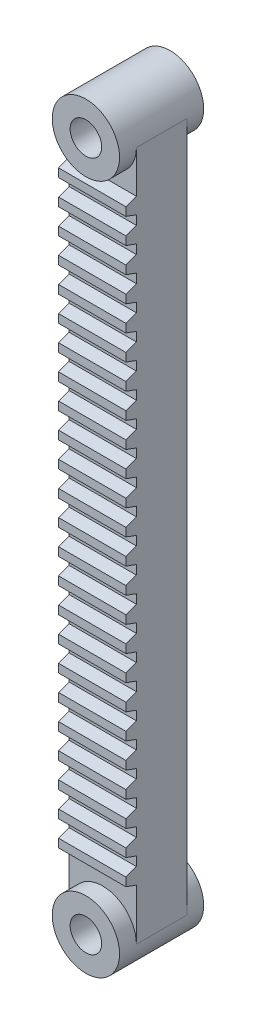
SolidWorks part; units mm, degrees
ref_plane "Front Plane" through (0, 0, 0) normal (1, 0, 0) x (0, 1, 0)
ref_plane "Top Plane" through (0, 0, 0) normal (0, 0, 1) x (0, 1, 0)
ref_plane "Right Plane" through (0, 0, 0) normal (0, 1, 0) x (-1, 0, 0)
sketch "Sketch3" plane through (0, 0, 0) normal (0, 0, 1) x (0, 1, 0)
  line L1 (-82, -8) -> (82, -8)
  line L3 (-82, 8) -> (82, 8)
  line L5 (-82, -8) -> (82, 8) construction
  line L6 (-82, 8) -> (82, -8) construction
  circle A0 centre (-82, 0) radius 8
  circle A1 centre (82, 0) radius 8
  circle A2 centre (-82, 0) radius 3.75
  circle A3 centre (82, 0) radius 3.75
  point P0 (0, 0)
  dimension "D1" = 16
  dimension "D2" = 16
  dimension "D5" = 7.5
  dimension "D6" = 7.5
  dimension "D3" = 164
  dimension "D4" = 16
extrude "Boss-Extrude1" add sketch "Sketch3" along normal blind 12 contours A1 L3 A0 L1 region at (0, 0, 0)
extrude "Boss-Extrude2" add sketch "Sketch3<3>" along normal blind 20 from offset 4 contours A0 A2 | A1 A3 region at (0, -89.7737, 0) region at (0, 74.2263, 0) offset against normal yes
sketch "Sketch3<3>" plane through (0, 0, 0) normal (0, 0, 1) x (0, 1, 0) same geometry as "Sketch3"
sketch "Sketch4" plane through (0, 0, 0) normal (1, 0, 0) x (0, 1, 0)
  line L0 (72, 12) -> (71.0901, 14.5)
  line L1 (-82, 12) -> (82, 12) construction
  line L2 (71.0901, 14.5) -> (69.0901, 14.5)
  line L3 (69.0901, 14.5) -> (68.1801, 12)
  line L4 (68.1801, 12) -> (72, 12)
  dimension "D1" = 2.5
  dimension "D2" = 2
  dimension "D3" = 40
  dimension "D4" = 70
  dimension "D5" = 70
  dimension "D6" = 18
extrude "Boss-Extrude3" add sketch "Sketch4" against normal mid plane 16
pattern_linear "LPattern1" count 24 spacing 6 along (0, -1, 0) of "Boss-Extrude3"
